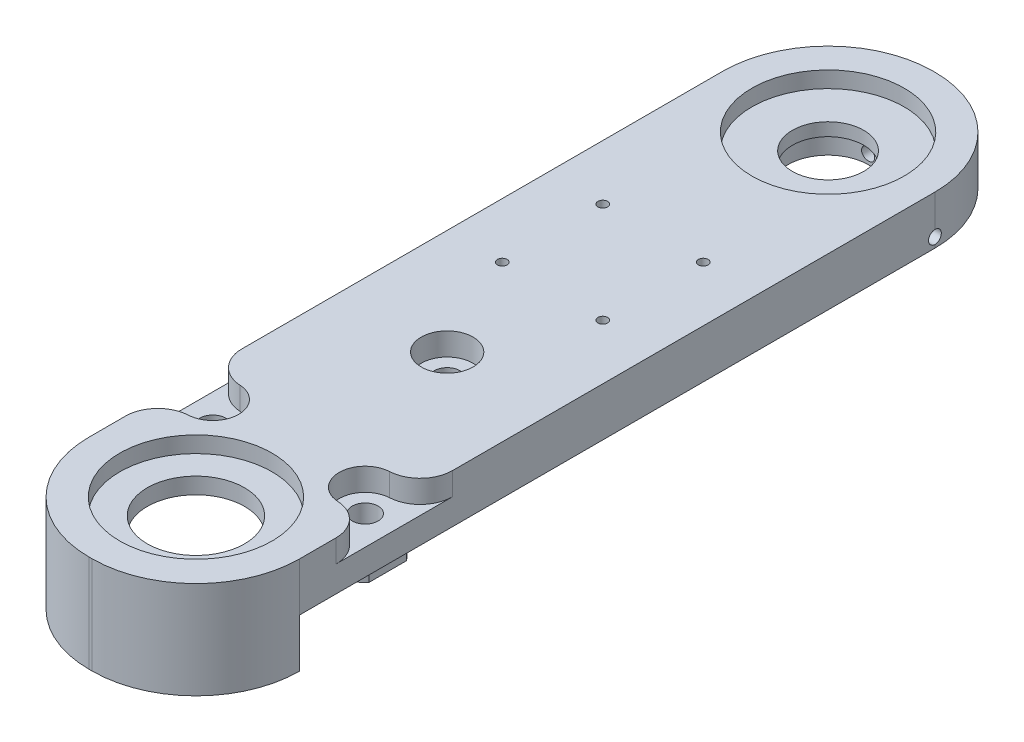
SolidWorks part; units mm, degrees
ref_plane "Front Plane" through (0, 0, 0) normal (0, 0, 1) x (1, 0, 0)
ref_plane "Top Plane" through (0, 0, 0) normal (0, 1, 0) x (1, 0, 0)
ref_plane "Right Plane" through (0, 0, 0) normal (1, 0, 0) x (0, 0, -1)
sketch "Sketch1" plane through (0, 0, 0) normal (0, 1, 0) x (1, 0, 0)
  line L1 (0, 130) -> (0.5, 130)
  line L2 (-32.5, 97.5) -> (-32.5, -98)
  line L3 (-0.5, -130) -> (0.5, -130)
  line L4 (32.5, 98) -> (32.5, -98)
  arc A0 (0, 130) -> (-32.5, 97.5) centre (0, 97.5) ccw
  arc A1 (0.5, -130) -> (32.5, -98) centre (0.5, -98) ccw
  arc A2 (-32.5, -98) -> (-0.5, -130) centre (-0.5, -98) ccw
  arc A3 (0.5, 130) -> (32.5, 98) centre (0.5, 98) cw
  point P1 (0, 0)
  dimension "D1" = 32.5
  dimension "D2" = 32
  dimension "D3" = 260.0005
extrude "Boss-Extrude1" add sketch "Sketch1" along normal blind 15
sketch "Sketch2" plane through (0, 15, 0) normal (0, 1, 0) x (1, 0, 0)
  line L0 (0, 130) -> (0, 97.5) construction
  circle A0 centre (0, 97.5) radius 23.5
extrude "Cut-Extrude1" cut sketch "Sketch2" against normal blind 5
sketch "Sketch3" plane through (0, 10, 0) normal (0, 1, 0) x (1, 0, 0)
  circle A2 centre (0, 97.5) radius 11
  circle A3 centre (0, 97.5) radius 11
  dimension "D1" = 12.5
extrude "Cut-Extrude2" cut sketch "Sketch3" against normal through all
sketch "Sketch17" plane through (0, 0, 0) normal (0, -1, 0) x (1, 0, 0)
  line L0 (0, 130) -> (0, 97.5) construction
  line L1 (-0.5, 130) -> (0.5, 130) construction
  circle A0 centre (0, 97.5) radius 23.5
extrude "Cut-Extrude10" cut sketch "Sketch17" against normal blind 5
sketch "Sketch18" plane through (0, 5, 0) normal (0, -1, 0) x (1, 0, 0)
  circle A0 centre (0, 97.5) radius 15
extrude "Cut-Extrude11" cut sketch "Sketch18" against normal through all
sketch "Sketch19" plane through (0, 15, 0) normal (0, 1, 0) x (1, 0, 0)
  circle A0 centre (0, -97.5) radius 23.5
extrude "Cut-Extrude12" cut sketch "Sketch19" against normal blind 5
sketch "Sketch20" plane through (0, 0, 0) normal (0, -1, 0) x (1, 0, 0)
  line L1 (-20, 0) -> (20, 0)
  line L2 (-30, -10) -> (-30, -60)
  line L3 (-20, -70) -> (20, -70)
  line L4 (30, -10) -> (30, -60)
  line L5 (-30, 0) -> (30, -70) construction
  line L6 (-30, -70) -> (30, 0) construction
  arc A0 (20, -70) -> (30, -60) centre (20, -60) ccw
  arc A1 (-30, -60) -> (-20, -70) centre (-20, -60) ccw
  arc A2 (20, 0) -> (30, -10) centre (20, -10) cw
  arc A3 (-20, 0) -> (-30, -10) centre (-20, -10) ccw
  point P0 (0, -35)
  dimension "D2" = 10
  dimension "D1" = 35
extrude "Cut-Extrude13" cut sketch "Sketch20" against normal blind 10
sketch "Sketch21" plane through (0, 10, 0) normal (0, -1, 0) x (1, 0, 0)
  line L1 (-15.5, -12.5) -> (15.5, -12.5) construction
  line L2 (-15.5, -12.5) -> (-15.5, -43.5) construction
  line L3 (-15.5, -43.5) -> (15.5, -43.5) construction
  line L4 (15.5, -12.5) -> (15.5, -43.5) construction
  line L5 (-15.5, -12.5) -> (15.5, -43.5) construction
  line L6 (-15.5, -43.5) -> (15.5, -12.5) construction
  circle A0 centre (-15.5, -12.5) radius 1.5
  circle A1 centre (15.5, -12.5) radius 1.5
  circle A2 centre (-15.5, -43.5) radius 1.5
  circle A3 centre (15.5, -43.5) radius 1.5
  point P0 (0, -28)
  dimension "D1" = 28
extrude "Cut-Extrude14" cut sketch "Sketch21" against normal through all
sketch "Sketch22" plane through (0, 0, 0) normal (0, -1, 0) x (1, 0, 0)
  line L0 (0, 97.5) -> (0, 0) construction
  circle A0 centre (0, 48.75) radius 8
extrude "Cut-Extrude15" cut sketch "Sketch22" against normal blind 4
sketch "Sketch23" plane through (0, 0, 0) normal (0, -1, 0) x (1, 0, 0)
  line L0 (-30.5, 74.6165) -> (-30.5, 62.9931)
  line L1 (-32.5, -97.5) -> (-32.5, 98) construction
  line L2 (0, -8.25) -> (0, 8.25) construction
  line L3 (30.5, 74.6165) -> (30.5, 62.9931)
  circle A1 centre (-23.5, 68.8048) radius 4
  arc A2 (-30.5, 62.9931) -> (-30.5, 74.6165) centre (-23.5, 68.8048) ccw
  circle A3 centre (23.5, 68.8048) radius 4
  arc A4 (30.5, 62.9931) -> (30.5, 74.6165) centre (23.5, 68.8048) cw
  dimension "D1" = 2
  dimension "D2" = 7
extrude "Boss-Extrude6" add sketch "Sketch23" along normal blind 4
sketch "Sketch24" plane through (0, 0, 0) normal (0, -1, 0) x (1, 0, 0)
  line L0 (20, 0) -> (-20, 0) construction
  line L1 (-0.5, 130) -> (0.5, 130) construction
  circle A0 centre (0, 20) radius 4
  circle A2 centre (-23.5, 68.8048) radius 4
  circle A3 centre (-23.5, 68.8048) radius 4
  circle A4 centre (23.5, 68.8048) radius 4
  circle A5 centre (23.5, 68.8048) radius 4
  point P12 (0, 130)
  dimension "D1" = 0
  dimension "D3" = 20
  dimension "D4" = 110
  dimension "D2" = 0
extrude "Cut-Extrude16" cut sketch "Sketch24" against normal through all
sketch "Sketch27" plane through (0, 0, 0) normal (0, -1, 0) x (1, 0, 0)
  line L0 (-0.5, 128) -> (0.5, 128)
  line L1 (-0.5, 130) -> (0.5, 130)
  line L2 (-30.5, 98) -> (-32.5, 98)
  line L3 (30.5, 98) -> (32.5, 98)
  arc A2 (-0.5, 130) -> (-32.5, 98) centre (-0.5, 98) ccw construction
  arc A3 (-0.5, 128) -> (-30.5, 98) centre (-0.5, 98) ccw
  arc A4 (-0.5, 128) -> (-30.5, 98) centre (-0.5, 98) ccw
  arc A5 (-0.5, 130) -> (-32.5, 98) centre (-0.5, 98) ccw
  arc A6 (32.5, 98) -> (0.5, 130) centre (0.5, 98) ccw construction
  arc A7 (32.5, 98) -> (0.5, 130) centre (0.5, 98) ccw
  arc A8 (30.5, 98) -> (0.5, 128) centre (0.5, 98) ccw
  dimension "D1" = 2
  dimension "D2" = 2
extrude "Boss-Extrude8" add sketch "Sketch27" along normal blind 15
sketch "Sketch28" plane through (0, 15, 0) normal (0, 1, 0) x (1, 0, 0)
  line L0 (-23.5, -60.8048) -> (-32.5, -60.8048)
  line L1 (-32.5, 97.5) -> (-32.5, -98) construction
  line L2 (-32.5, -60.8048) -> (-32.5, -76.8048)
  line L3 (-32.5, -76.8048) -> (-23.5, -76.8048)
  line L4 (0, -10.45) -> (0, 10.45) construction
  line L5 (32.5, -60.8048) -> (32.5, -76.8048)
  line L6 (23.5, -60.8048) -> (32.5, -60.8048)
  line L7 (32.5, -76.8048) -> (23.5, -76.8048)
  arc A0 (-23.5, -60.8048) -> (-23.5, -76.8048) centre (-23.5, -68.8048) cw
  arc A1 (23.5, -60.8048) -> (23.5, -76.8048) centre (23.5, -68.8048) ccw
  circle A3 centre (0, -20) radius 8
extrude "Cut-Extrude17" cut sketch "Sketch28" against normal blind 7
fillet "Fillet1" radius 10 4 edges at (32.5, 11.5, 76.8048) (32.5, 11.5, 60.8048) (-32.5, 11.5, 76.8048) (-32.5, 11.5, 60.8048)
sketch "Sketch29" plane through (0, 0, 0) normal (0, -1, 0) x (1, 0, 0)
  circle A0 centre (0, -97.5) radius 12.5
extrude "Cut-Extrude18" cut sketch "Sketch29" against normal blind 6
sketch "Sketch30" plane through (0, 0, -130) normal (0, 0, -1) x (-1, 0, 0)
  line L0 (0, 15) -> (0, 0) construction
  circle A0 centre (0, 3) radius 2
  dimension "D1" = 3
extrude "Cut-Extrude19" cut sketch "Sketch30" against normal blind 25
sketch "Sketch32" plane through (32.5, 0, 0) normal (1, 0, 0) x (0, 0, -1)
  line L0 (98, 15) -> (98, 0) construction
  circle A0 centre (98, 3) radius 2
  dimension "D1" = 3
extrude "Cut-Extrude20" cut sketch "Sketch32" against normal blind 25
equation "\"n\"= 60"
equation "\"p\"= 2"
equation "\"pd\"= \"n\" * \"p\" / pi"
